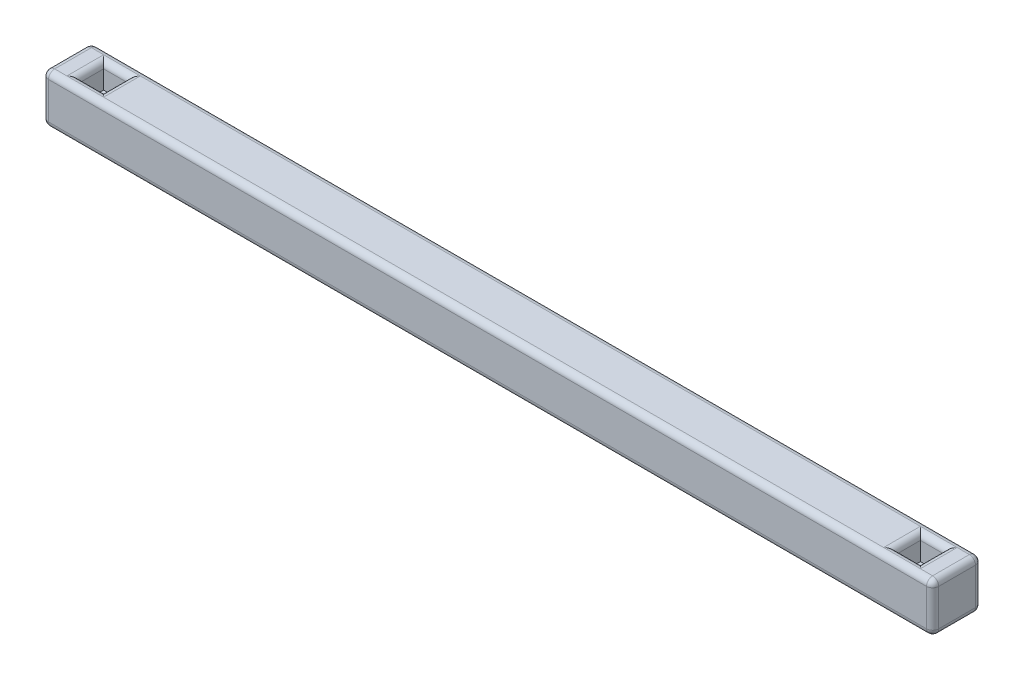
SolidWorks part; units mm, degrees
ref_plane "Front Plane" through (0, 0, 0) normal (0, 0, 1) x (1, 0, 0)
ref_plane "Top Plane" through (0, 0, 0) normal (0, 1, 0) x (1, 0, 0)
ref_plane "Right Plane" through (0, 0, 0) normal (1, 0, 0) x (0, 0, -1)
sketch "Sketch1" plane through (0, 0, 0) normal (0, 1, 0) x (1, 0, 0)
  line L1 (0, 0) -> (230.8225, 0)
  line L2 (0, 0) -> (0, 12.7)
  line L3 (0, 12.7) -> (230.8225, 12.7)
  line L4 (230.8225, 0) -> (230.8225, 12.7)
  dimension "D1" = 230.8225
  dimension "D2" = 12.7
extrude "Boss-Extrude1" add sketch "Sketch1" along normal blind 12.7 contours L3 L4 L1 L2
sketch "Sketch2" plane through (0, 12.7, 0) normal (0, 1, 0) x (1, 0, 0)
  line L0 (230.8225, 0) -> (230.8225, 12.7) construction
  line L1 (218.1225, 9.525) -> (224.4725, 9.525)
  line L2 (218.1225, 9.525) -> (218.1225, 3.175)
  line L3 (218.1225, 3.175) -> (224.4725, 3.175)
  line L4 (224.4725, 9.525) -> (224.4725, 3.175)
  line L5 (221.2975, 9.525) -> (221.2975, 12.7) construction
  line L6 (0, 12.7) -> (230.8225, 12.7) construction
  line L7 (221.2975, 3.175) -> (221.2975, 0) construction
  line L8 (0, 0) -> (230.8225, 0) construction
  line L9 (115.4113, 12.7) -> (115.4113, 0) construction
  line L10 (12.7, 3.175) -> (6.35, 3.175)
  line L11 (6.35, 9.525) -> (6.35, 3.175)
  line L12 (12.7, 9.525) -> (6.35, 9.525)
  line L13 (12.7, 9.525) -> (12.7, 3.175)
  point P4 (221.2975, 9.525)
  point P8 (230.8225, 6.35)
  dimension "D1" = 6.35
  dimension "D2" = 6.35
extrude "Cut-Extrude1" cut sketch "Sketch2" against normal blind 6.35
fillet "Fillet1" radius 1.5875 20 edges at (230.8225, 0, -6.35) (0, 0, -6.35) (230.8225, 6.35, -12.7) (0, 6.35, -12.7) (115.4113, 0, -12.7) (115.4113, 12.7, -12.7) (230.8225, 12.7, -6.35) (0, 12.7, -6.35) (6.35, 12.7, -6.35) (9.525, 12.7, -3.175) (12.7, 12.7, -6.35) (9.525, 12.7, -9.525) (224.4725, 12.7, -6.35) (221.2975, 12.7, -9.525) (218.1225, 12.7, -6.35) (221.2975, 12.7, -3.175) (0, 6.35, 0) (115.4113, 12.7, 0) (230.8225, 6.35, 0) (115.4113, 0, 0)
sketch "Sketch3" plane through (0, 0, 0) normal (0, -1, 0) x (1, 0, 0)
  line L0 (9.525, -6.35) -> (9.525, 0) construction
  line L1 (1.5875, 0) -> (229.235, 0) construction
  line L2 (9.525, -6.35) -> (9.525, -12.7) construction
  line L3 (229.235, -12.7) -> (1.5875, -12.7) construction
  line L4 (0, -11.1125) -> (0, -1.5875) construction
  line L5 (230.8225, -1.5875) -> (230.8225, -11.1125) construction
  circle A0 centre (9.525, -6.35) radius 2.286
  circle A1 centre (221.2975, -6.35) radius 2.286
  point P4 (0, 0)
  point P15 (6.35, -6.35)
  dimension "D1" = 4.572
  dimension "D2" = 9.525
  dimension "D3" = 9.525
extrude "Cut-Extrude2" cut sketch "Sketch3" against normal through all
